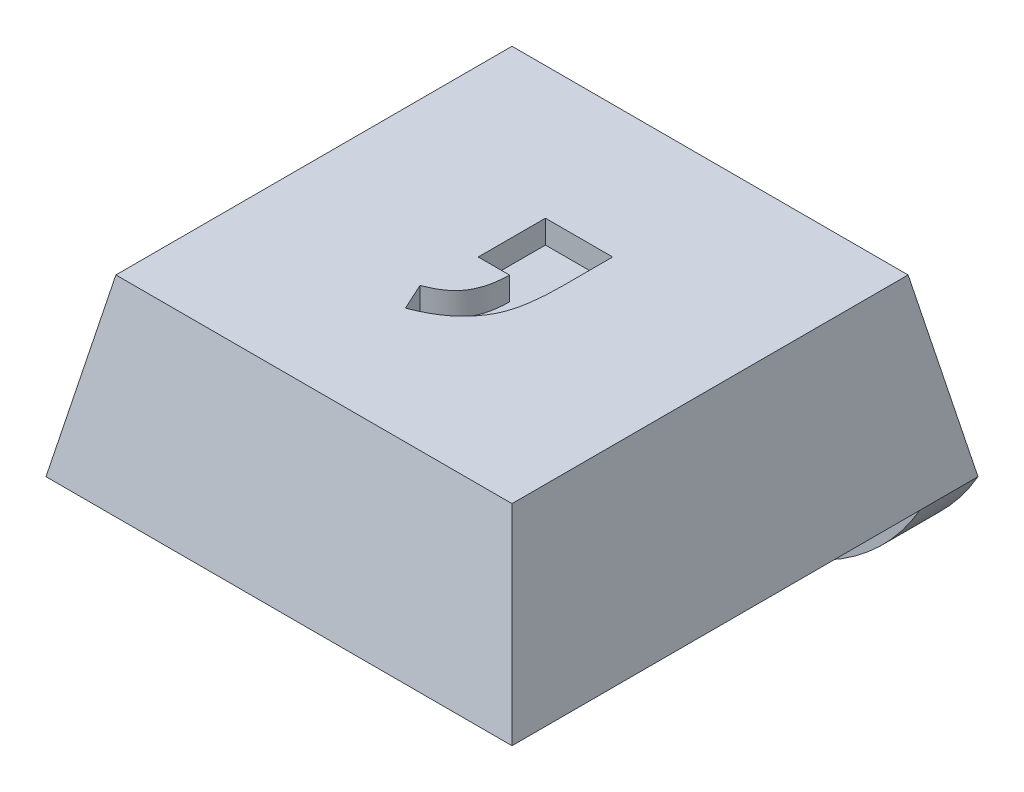
SolidWorks part; units mm, degrees
ref_plane "Front Plane" through (0, 0, 0) normal (0, 0, 1) x (1, 0, 0)
ref_plane "Top Plane" through (0, 0, 0) normal (0, 1, 0) x (1, 0, 0)
ref_plane "Right Plane" through (0, 0, 0) normal (1, 0, 0) x (0, 0, -1)
sketch "Sketch1" plane through (0, 0, 0) normal (0, 1, 0) x (1, 0, 0)
  line L1 (0, 0) -> (8, 0)
  line L2 (0, 0) -> (0, 8)
  line L3 (0, 8) -> (8, 8)
  line L4 (8, 0) -> (8, 8)
  dimension "D1" = 8
  dimension "D2" = 8
extrude "Boss-Extrude1" add sketch "Sketch1" along normal blind 3
sketch "Sketch2" plane through (0, 0, 0) normal (0, 0, 1) x (1, 0, 0)
  line L0 (0, 0) -> (0.6, 3)
  line L1 (0, 3) -> (8, 3) construction
  line L2 (0.6, 3) -> (0, 3)
  line L3 (0, 3) -> (0, 0)
  line L4 (8, 0) -> (7.4, 3)
  line L5 (7.4, 3) -> (8, 3)
  line L6 (8, 3) -> (8, 0)
  dimension "D1" = 0.6
  dimension "D2" = 0.6
extrude "Cut-Extrude1" cut sketch "Sketch2" against normal through all both and the other way through all
sketch "Sketch3" plane through (0, 0, 0) normal (1, 0, 0) x (0, 0, -1)
  line L0 (0, 0) -> (0.6, 3)
  line L1 (8, 3) -> (0, 3) construction
  line L2 (0.6, 3) -> (0, 3)
  line L3 (0, 3) -> (0, 0)
  line L4 (8, 3) -> (7.4, 3)
  line L5 (7.4, 3) -> (8, 0)
  line L6 (8, 3) -> (8, 0)
  dimension "D1" = 0.6
  dimension "D2" = 0.6
extrude "Cut-Extrude2" cut sketch "Sketch3" along normal blind 11
sketch "Sketch4" plane through (0, 0, 0) normal (0, -1, 0) x (1, 0, 0)
  line L0 (8, 0) -> (8, -8) construction
  line L3 (0, 0) -> (8, 0) construction
  circle A0 centre (4, -3.75) radius 1.8
  dimension "D1" = 3.6
  dimension "D2" = 4
  dimension "D3" = 3.75
extrude "Cut-Extrude3" cut sketch "Sketch4" against normal blind 0.8
sketch "Sketch5" plane through (0, 0, 0) normal (0, -1, 0) x (1, 0, 0)
  line L0 (8, 0) -> (8, -8) construction
  line L1 (0, -8) -> (8, -8)
  line L2 (0, -8) -> (0, -7)
  line L3 (0, -7) -> (8, -7)
  line L4 (8, -8) -> (8, -7)
  dimension "D1" = 1
extrude "Boss-Extrude2" add sketch "Sketch5" along normal blind 2
fillet "Fillet1" radius 4 2 edges at (8, -2, -7.5) (0, -2, -7.5)
sketch "Sketch6" plane through (0, 3, 0) normal (0, 1, 0) x (1, 0, 0)
  text T0 "," font "Arial" height 6
extrude "Cut-Extrude4" cut sketch "Sketch6" against normal blind 0.4
